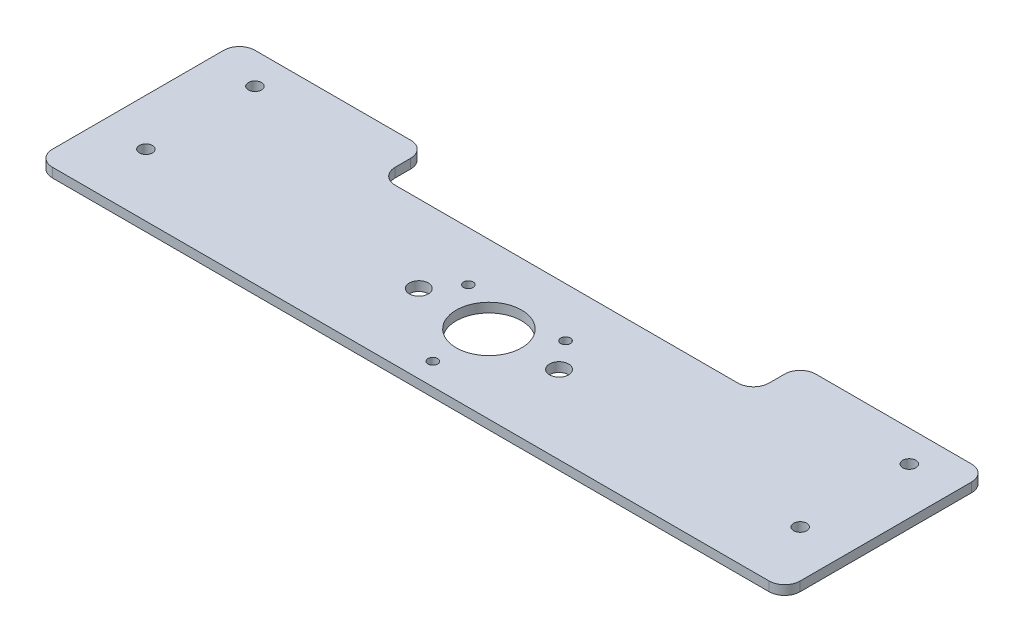
SolidWorks part; units mm, degrees
material "Thornel Mat VMA"
ref_plane "前视基准面" through (0, 0, 0) normal (0, 0, 1) x (1, 0, 0)
ref_plane "上视基准面" through (0, 0, 0) normal (0, 1, 0) x (1, 0, 0)
ref_plane "右视基准面" through (0, 0, 0) normal (1, 0, 0) x (0, 0, -1)
sketch "草图1" plane through (0, 0, 0) normal (0, 1, 0) x (1, 0, 0)
  line L0 (-105, 57.5) -> (-105, -7.5) construction
  line L1 (-120, -7.5) -> (120, -7.5)
  line L2 (-120, -7.5) -> (-120, 57.5)
  line L3 (-120, 57.5) -> (120, 57.5)
  line L4 (120, -7.5) -> (120, 57.5)
  line L5 (-120, -7.5) -> (120, 57.5) construction
  line L6 (-120, 57.5) -> (120, -7.5) construction
  line L7 (0, 57.5) -> (0, -7.5) construction
  line L8 (0, -57.5) -> (0, -7.5) construction
  line L9 (-60, -7.5) -> (20, -7.5)
  circle A0 centre (-105, 47.5) radius 2.1
  circle A1 centre (-105, 12.5) radius 2.1
  circle A2 centre (105, 12.5) radius 2.1
  circle A3 centre (105, 47.5) radius 2.1
  point P0 (0, 25)
  dimension "D1" = 65
  dimension "D2" = 240
  dimension "D3" = 15
  dimension "D4" = 35
  dimension "D5" = 20
extrude "凸台-拉伸1" add sketch "草图1" along normal blind 3 contours L1 L4 L3 L2 A2 A1 A0 A3 region at (0, 0, -24.9822)
sketch "草图2" plane through (0, 3, 0) normal (0, 1, 0) x (1, 0, 0)
  line L0 (0, 57.5) -> (0, -7.5) construction
  line L1 (-120, 57.5) -> (120, 57.5) construction
  line L2 (-120, -7.5) -> (120, -7.5) construction
  line L3 (-60, 57.5) -> (-60, 42.5)
  line L4 (-60, 42.5) -> (60, 42.5)
  line L5 (60, 57.5) -> (60, 42.5)
  line L6 (-60, 57.5) -> (60, 57.5)
  point P10 (0, 42.5)
  dimension "D1" = 15
  dimension "D2" = 60
extrude "切除-拉伸1" cut sketch "草图2" against normal blind 3
fillet "圆角1" radius 5 8 edges at (120, 1.5, 7.5) (-120, 1.5, 7.5) (-120, 1.5, -57.5) (120, 1.5, -57.5) (60, 1.5, -57.5) (60, 1.5, -42.5) (-60, 1.5, -42.5) (-60, 1.5, -57.5)
sketch "草图3" plane through (0, 3, 0) normal (0, 1, 0) x (1, 0, 0)
  line L0 (-55, 42.5) -> (55, 42.5) construction
  line L1 (-55, 42.5) -> (55, 42.5)
  line L2 (0, 42.5) -> (0, -7.3132) construction
  circle A0 centre (0, 17.5934) radius 10.5
  circle A1 centre (0, -0.4066) radius 1.55
  circle A2 centre (-15.5885, 26.5934) radius 1.55
  circle A3 centre (15.5885, 26.5934) radius 1.55
  point P16 (0, 17.5934)
  dimension "D1" = 3
extrude "切除-拉伸2" cut sketch "草图3" against normal blind 32 contours L2 A0 | A0 L2 | A3 | L2 A1 | A1 L2 | A2 region at (4.4563, 3, -17.5934) region at (0.6578, 3, 0.4066) region at (-0.6578, 3, 0.4066) region at (-4.4563, 3, -17.5934) region at (-15.5885, 3, -26.5934) region at (15.5885, 3, -26.5934)
sketch "草图4" plane through (0, 3, 0) normal (0, 1, 0) x (1, 0, 0)
  line L0 (22.5, 17.5934) -> (-22.5, 17.5934) construction
  circle A0 centre (0, 17.5934) radius 10.5 construction
  circle A1 centre (0, 17.5934) radius 10.5 construction
  circle A2 centre (-22.5, 17.5934) radius 3.05
  circle A3 centre (22.5, 17.5934) radius 3.05
  point P5 (0, 17.5934)
  dimension "D1" = 22.5
extrude "切除-拉伸3" cut sketch "草图4" against normal blind 10
